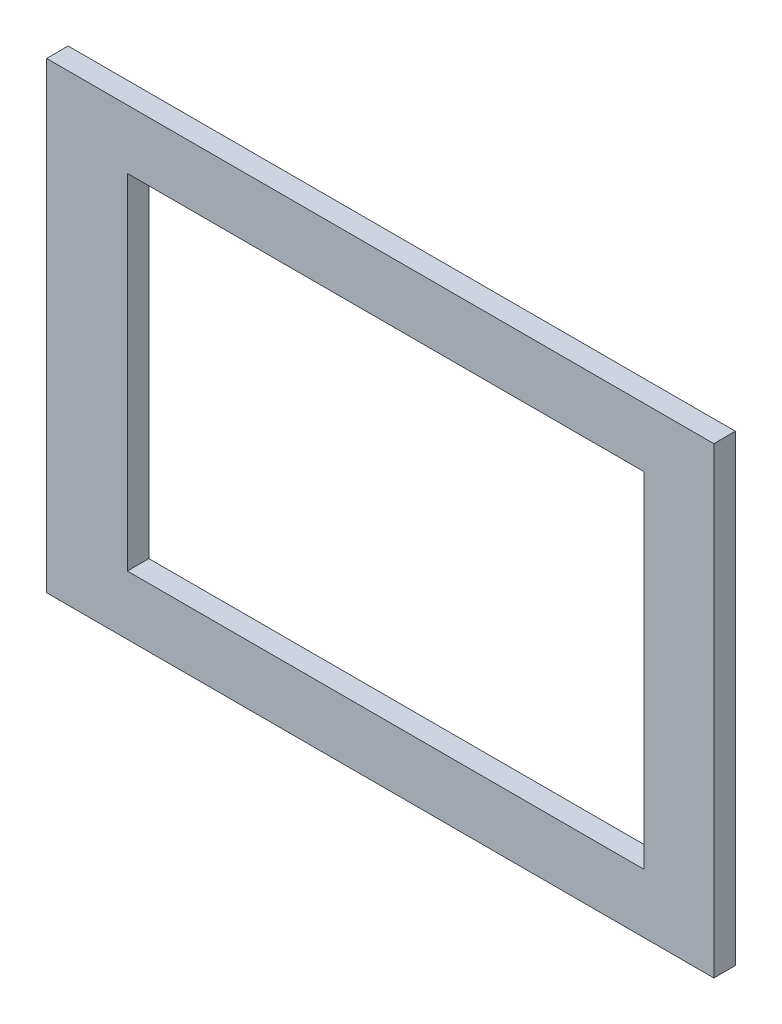
SolidWorks part; units mm, degrees
ref_plane "Front Plane" through (0, 0, 0) normal (0, 0, 1) x (1, 0, 0)
ref_plane "Top Plane" through (0, 0, 0) normal (0, 1, 0) x (1, 0, 0)
ref_plane "Right Plane" through (0, 0, 0) normal (1, 0, 0) x (0, 0, -1)
sketch "Sketch1" plane through (0, 0, 0) normal (0, 0, 1) x (1, 0, 0)
  line L1 (65.2195, -7.9375) -> (-131.6305, -7.9375)
  line L2 (65.2195, -7.9375) -> (65.2195, -144.4625)
  line L3 (65.2195, -144.4625) -> (-131.6305, -144.4625)
  line L4 (-131.6305, -7.9375) -> (-131.6305, -144.4625)
extrude "Boss-Extrude1" add sketch "Sketch1" along normal blind 6.35
sketch "Sketch2" plane through (0, 0, 6.35) normal (0, 0, 1) x (1, 0, 0)
  line L0 (-91.2922, -76.2) -> (25.6431, -76.2) construction
  line L1 (44.582, -25.4) -> (-107.818, -25.4)
  line L2 (44.582, -25.4) -> (44.582, -127)
  line L3 (44.582, -127) -> (-107.818, -127)
  line L4 (-107.818, -25.4) -> (-107.818, -127)
  line L5 (-131.6305, -144.4625) -> (65.2195, -144.4625) construction
  line L6 (65.2195, -7.9375) -> (-131.6305, -7.9375) construction
  line L7 (-131.6305, -7.9375) -> (-131.6305, -144.4625) construction
  dimension "D1" = 101.6
  dimension "D2" = 152.4
  dimension "D3" = 23.8125
extrude "Cut-Extrude1" cut sketch "Sketch2" against normal through all
